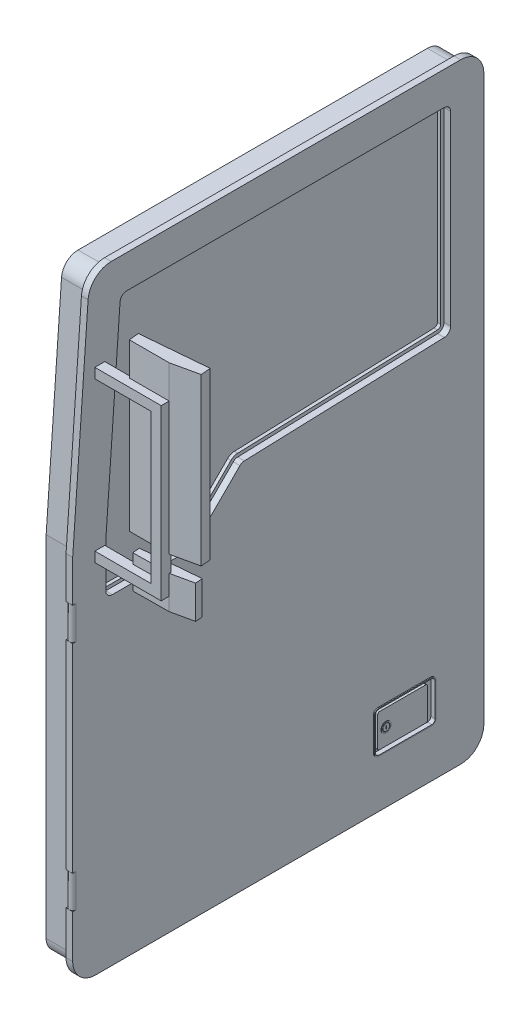
SolidWorks part; units mm, degrees
ref_plane "Front Plane" through (0, 0, 0) normal (0, 0, 1) x (1, 0, 0)
ref_plane "Top Plane" through (0, 0, 0) normal (0, 1, 0) x (1, 0, 0)
ref_plane "Right Plane" through (0, 0, 0) normal (1, 0, 0) x (0, 0, -1)
ref_plane "Plane1" through (950, 0, 0) normal (1, 0, 0) x (0, 0, -1)
sketch "Sketch1" plane through (950, 0, 0) normal (1, 0, 0) x (0, 0, -1)
  line L0 (-750, -200) -> (-750, 1110) construction
  line L1 (-550, 0) -> (550, 0)
  line L2 (-600, 50) -> (-600, 1104.6439)
  line L3 (-503.7259, 1800) -> (550, 1800)
  line L4 (600, 50) -> (600, 1750)
  line L5 (-750, 1110) -> (-699.9479, 1809.9761) construction
  line L6 (-699.9479, 1809.9761) -> (-739.9479, 1809.9761) construction
  line L7 (-739.9479, 1809.9761) -> (-739.9479, 1909.9761) construction
  line L8 (-750, -200) -> (600, -200) construction
  line L9 (600, -200) -> (600, 0) construction
  line L10 (-600, 1104.6439) -> (-553.5985, 1753.5662)
  line L11 (-503.7259, 1820) -> (550, 1820)
  line L12 (620, 50) -> (620, 1750)
  line L13 (-550, -20) -> (550, -20)
  line L14 (-620, 50) -> (-620, 1105.3581)
  line L15 (-620, 1105.3581) -> (-573.5476, 1754.9926)
  arc A0 (-553.5985, 1753.5662) -> (-503.7259, 1800) centre (-503.7259, 1750) cw
  arc A1 (550, 1800) -> (600, 1750) centre (550, 1750) cw
  arc A2 (550, 0) -> (600, 50) centre (550, 50) ccw
  arc A3 (-550, 0) -> (-600, 50) centre (-550, 50) cw
  arc A4 (550, 1820) -> (620, 1750) centre (550, 1750) cw
  arc A5 (550, -20) -> (620, 50) centre (550, 50) ccw
  arc A6 (-550, -20) -> (-620, 50) centre (-550, 50) cw
  arc A7 (-573.5476, 1754.9926) -> (-503.7259, 1820) centre (-503.7259, 1750) cw
  point P16 (600, 1800)
  point P22 (-600, 0)
  dimension "D11" = 50
  dimension "D1" = 1200
  dimension "D2" = 1800
  dimension "D3" = 200
  dimension "D4" = 100
  dimension "D5" = 40
  dimension "D6" = 2110
  dimension "D7" = 150
  dimension "D8" = 1310
  dimension "D9" = 175.91
  dimension "D10" = 150
  dimension "D12" = 20
extrude "Boss-Extrude1" add sketch "Sketch1" against normal blind 20
extrude "Boss-Extrude2" add sketch "Sketch1<2>" against normal blind 100 contours A3 L1 A2 L4 A1 L3 A0 L10 L2 region at (950, 894.6381, -4.6785)
sketch "Sketch1<2>" plane through (950, 0, 0) normal (1, 0, 0) x (0, 0, -1) same geometry as "Sketch1"
sketch "Sketch2" plane through (950, 0, 0) normal (1, 0, 0) x (0, 0, -1)
  line L9 (-520.2547, 1098.2257) -> (-520.2547, 968.2257)
  line L10 (-500.2547, 948.2257) -> (-268.6753, 948.2257)
  line L11 (-254.5499, 954.0669) -> (-115.6202, 1092.6683)
  line L12 (520, 50) -> (520, 1720)
  line L13 (520, 1720) -> (-475.7944, 1720)
  line L14 (-475.7944, 1720) -> (-520.2547, 1098.2257)
  line L15 (520, 1139.3207) -> (520, 1700)
  line L16 (500, 1720) -> (-457.1735, 1720)
  line L17 (-477.1225, 1701.4265) -> (-520.2547, 1098.2257)
  line L18 (-102.1855, 1098.4975) -> (500.6908, 1119.3327)
  line L19 (500, 1710) -> (-457.1735, 1710)
  line L20 (-467.148, 1700.7132) -> (-510.2547, 1097.8687)
  line L21 (-510.2547, 1097.8687) -> (-510.2547, 968.2257)
  line L22 (-500.2547, 958.2257) -> (-268.6753, 958.2257)
  line L23 (-261.6126, 961.1463) -> (-122.6829, 1099.7477)
  line L24 (-102.5309, 1108.4915) -> (500.3454, 1129.3267)
  line L25 (510, 1139.3207) -> (510, 1700)
  arc A6 (520, 1700) -> (500, 1720) centre (500, 1700) ccw
  arc A7 (500.6908, 1119.3327) -> (520, 1139.3207) centre (500, 1139.3207) ccw
  arc A8 (-115.6202, 1092.6683) -> (-102.1855, 1098.4975) centre (-101.4948, 1078.5094) cw
  arc A9 (-268.6753, 948.2257) -> (-254.5499, 954.0669) centre (-268.6753, 968.2257) ccw
  arc A10 (-457.1735, 1720) -> (-477.1225, 1701.4265) centre (-457.1735, 1700) ccw
  arc A11 (-520.2547, 968.2257) -> (-500.2547, 948.2257) centre (-500.2547, 968.2257) ccw
  arc A12 (-457.1735, 1710) -> (-467.148, 1700.7132) centre (-457.1735, 1700) ccw
  arc A13 (-510.2547, 968.2257) -> (-500.2547, 958.2257) centre (-500.2547, 968.2257) ccw
  arc A14 (-268.6753, 958.2257) -> (-261.6126, 961.1463) centre (-268.6753, 968.2257) ccw
  arc A15 (-122.6829, 1099.7477) -> (-102.5309, 1108.4915) centre (-101.4948, 1078.5094) cw
  arc A16 (500.3454, 1129.3267) -> (510, 1139.3207) centre (500, 1139.3207) ccw
  arc A17 (510, 1700) -> (500, 1710) centre (500, 1700) ccw
  point P13 (520, 1120)
  point P16 (-110.0496, 1098.2257)
  point P19 (-260.4048, 948.2257)
  point P25 (-520.2547, 948.2257)
  dimension "D6" = 20
  dimension "D2" = 600
  dimension "D3" = 621.7743
  dimension "D4" = 150
  dimension "D5" = 150
  dimension "D1" = 100
  dimension "D7" = 10
extrude "Cut-Extrude1" cut sketch "Sketch2" against normal blind 20
extrude "Cut-Extrude2" cut sketch "Sketch2<2>" against normal blind 30 contours L25 A17 L19 A12 L20 L21 A13 L22 A14 L23 A15 L24 A16 region at (950, 1382.3885, 18.9303)
sketch "Sketch2<2>" plane through (950, 0, 0) normal (1, 0, 0) x (0, 0, -1) same geometry as "Sketch2"
sketch "Sketch3" plane through (850, 0, 0) normal (-1, 0, 0) x (0, 0, 1)
  line L0 (-520, 1700) -> (-520, 1139.3207)
  line L1 (-500, 1710) -> (457.1735, 1710)
  line L2 (-500.6908, 1119.3327) -> (102.1855, 1098.4975)
  line L3 (115.6202, 1092.6683) -> (254.5499, 954.0669)
  line L4 (268.6753, 948.2257) -> (500.2547, 948.2257)
  line L5 (520.2547, 968.2257) -> (520.2547, 1098.2257)
  line L6 (520.2547, 1098.2257) -> (477.1225, 1701.4265)
  line L7 (-500, 1720) -> (457.1735, 1720)
  line L8 (510.2547, 1097.8687) -> (467.148, 1700.7132)
  line L9 (510.2547, 968.2257) -> (510.2547, 1097.8687)
  line L10 (268.6753, 958.2257) -> (500.2547, 958.2257)
  line L11 (122.6829, 1099.7477) -> (261.6126, 961.1463)
  line L12 (-500.3454, 1129.3267) -> (102.5309, 1108.4915)
  line L13 (-510, 1700) -> (-510, 1139.3207)
  arc A0 (-520, 1139.3207) -> (-500.6908, 1119.3327) centre (-500, 1139.3207) ccw
  arc A1 (102.1855, 1098.4975) -> (115.6202, 1092.6683) centre (101.4948, 1078.5094) cw
  arc A2 (254.5499, 954.0669) -> (268.6753, 948.2257) centre (268.6753, 968.2257) ccw
  arc A5 (254.5499, 954.0669) -> (268.6753, 948.2257) centre (268.6753, 968.2257) ccw construction
  arc A6 (500.2547, 948.2257) -> (520.2547, 968.2257) centre (500.2547, 968.2257) ccw
  arc A7 (457.1735, 1720) -> (477.1225, 1701.4265) centre (457.1735, 1700) cw
  arc A8 (-520, 1700) -> (-500, 1720) centre (-500, 1700) cw
  arc A9 (-510, 1700) -> (-500, 1710) centre (-500, 1700) cw
  arc A10 (457.1735, 1710) -> (467.148, 1700.7132) centre (457.1735, 1700) cw
  arc A11 (500.2547, 958.2257) -> (510.2547, 968.2257) centre (500.2547, 968.2257) ccw
  arc A12 (261.6126, 961.1463) -> (268.6753, 958.2257) centre (268.6753, 968.2257) ccw
  arc A13 (102.5309, 1108.4915) -> (122.6829, 1099.7477) centre (101.4948, 1078.5094) cw
  arc A14 (-510, 1139.3207) -> (-500.3454, 1129.3267) centre (-500, 1139.3207) ccw
  dimension "D1" = 10
extrude "Cut-Extrude3" cut sketch "Sketch3" against normal blind 20
extrude "Cut-Extrude4" cut sketch "Sketch3<2>" against normal blind 60 contours L13 A14 L12 A13 L11 A12 L10 A11 L9 L8 A10 L1 A9 region at (850, 1382.3885, 18.9303)
sketch "Sketch3<2>" plane through (850, 0, 0) normal (-1, 0, 0) x (0, 0, 1) same geometry as "Sketch3"
ref_plane "Plane2" through (0, 180, 0) normal (0, -1, 0) x (1, 0, 0)
sketch "Sketch4" plane through (0, 180, 0) normal (0, -1, 0) x (1, 0, 0)
  line L0 (930, 573.5476) -> (930, 620) construction
  line L2 (930, 620) -> (950, 620) construction
  line L3 (930, 610) -> (930, 624.5561)
  line L4 (930, 624.5561) -> (950, 624.5561)
  line L5 (950, 624.5561) -> (950, 610)
  circle A0 centre (940, 610) radius 10
  dimension "D1" = 20
extrude "Cut-Extrude5" cut sketch "Sketch4" against normal blind 100 contours A0 L5 L4 L3 region at (940, 180, 620.8334)
pattern_linear "LPattern1" count 2 spacing 700 along (0, 1, 0) of "Cut-Extrude5"
sketch "Sketch5" plane through (950, 0, 0) normal (1, 0, 0) x (0, 0, -1)
  line L0 (620, 50) -> (620, 1750) construction
  line L1 (460, 130) -> (300, 130)
  line L2 (470, 140) -> (470, 240)
  line L3 (460, 250) -> (300, 250)
  line L4 (290, 140) -> (290, 240)
  line L5 (-550, -20) -> (550, -20) construction
  line L6 (460, 253) -> (300, 253)
  line L7 (287, 140) -> (287, 240)
  line L8 (460, 127) -> (300, 127)
  line L9 (473, 140) -> (473, 240)
  arc A0 (470, 240) -> (460, 250) centre (460, 240) ccw
  arc A1 (460, 130) -> (470, 140) centre (460, 140) ccw
  arc A2 (300, 130) -> (290, 140) centre (300, 140) cw
  arc A3 (300, 250) -> (290, 240) centre (300, 240) ccw
  arc A4 (300, 253) -> (287, 240) centre (300, 240) ccw
  arc A5 (300, 127) -> (287, 140) centre (300, 140) cw
  arc A6 (460, 127) -> (473, 140) centre (460, 140) ccw
  arc A7 (473, 240) -> (460, 253) centre (460, 240) ccw
  point P10 (470, 250)
  point P13 (470, 130)
  point P16 (290, 130)
  dimension "D5" = 10
  dimension "D1" = 120
  dimension "D2" = 150
  dimension "D3" = 150
  dimension "D4" = 180
  dimension "D6" = 3
extrude "Cut-Extrude6" cut sketch "Sketch5" against normal blind 10 contours L3 A3 L4 A2 L1 A1 L2 A0 region at (950, 190, -380)
extrude "Boss-Extrude3" add sketch "Sketch5<3>" along normal blind 3
sketch "Sketch5<3>" plane through (950, 0, 0) normal (1, 0, 0) x (0, 0, -1) same geometry as "Sketch5"
sketch "Sketch6" plane through (940, 0, 0) normal (1, 0, 0) x (0, 0, -1)
  line L0 (300, 130) -> (460, 130) construction
  line L1 (305, 240) -> (445, 240)
  line L2 (300, 235) -> (300, 145)
  line L3 (305, 140) -> (445, 140)
  line L4 (450, 235) -> (450, 145)
  line L5 (290, 240) -> (290, 140) construction
  arc A0 (300, 145) -> (305, 140) centre (305, 145) ccw
  arc A1 (445, 140) -> (450, 145) centre (445, 145) ccw
  arc A2 (445, 240) -> (450, 235) centre (445, 235) cw
  arc A3 (305, 240) -> (300, 235) centre (305, 235) ccw
  point P10 (300, 140)
  point P15 (450, 240)
  point P18 (300, 240)
  dimension "D5" = 5
  dimension "D1" = 150
  dimension "D2" = 100
  dimension "D3" = 10
  dimension "D4" = 10
extrude "Boss-Extrude4" add sketch "Sketch6" along normal blind 10
sketch "Sketch10" plane through (950, 0, 0) normal (1, 0, 0) x (0, 0, -1)
  line L0 (324.7973, 190) -> (300, 190) construction
  line L1 (325.7973, 195) -> (323.7973, 195)
  line L2 (325.7973, 195) -> (325.7973, 185)
  line L3 (325.7973, 185) -> (323.7973, 185)
  line L4 (323.7973, 195) -> (323.7973, 185)
  line L5 (325.7973, 195) -> (323.7973, 185) construction
  line L6 (325.7973, 185) -> (323.7973, 195) construction
  line L7 (300, 235) -> (300, 145) construction
  circle A0 centre (324.7973, 190) radius 15
  dimension "D1" = 30
  dimension "D2" = 2
  dimension "D3" = 10
extrude "Boss-Extrude5" add sketch "Sketch10" along normal blind 1
extrude "Cut-Extrude8" cut sketch "Sketch10<2>" against normal blind 20 contours L1 L4 L3 L2 region at (950, 190, -324.7973)
sketch "Sketch10<2>" plane through (950, 0, 0) normal (1, 0, 0) x (0, 0, -1) same geometry as "Sketch10"
sketch "Sketch11" plane through (951, 0, 0) normal (1, 0, 0) x (0, 0, -1)
  circle A0 centre (324.7973, 190) radius 10.3287
extrude "Cut-Extrude-Thin1" cut sketch "Sketch11" against normal blind 5 thin thin type one direction wall 1
sketch "Sketch12" plane through (950, 0, 0) normal (1, 0, 0) x (0, 0, -1)
  line L0 (-477.1225, 1701.4265) -> (-520.2547, 1098.2257) construction
  line L1 (-523.1149, 1058.2257) -> (-553.1149, 1058.2257)
  line L2 (-523.1149, 1058.2257) -> (-523.1149, 1088.2257)
  line L3 (-523.1149, 1088.2257) -> (-553.1149, 1088.2257)
  line L4 (-553.1149, 1058.2257) -> (-553.1149, 1088.2257)
  line L5 (-500.2547, 958.2257) -> (-268.6753, 958.2257) construction
  line L6 (-523.1149, 1568.2257) -> (-553.1149, 1568.2257)
  line L7 (-523.1149, 1568.2257) -> (-523.1149, 1538.2257)
  line L8 (-523.1149, 1538.2257) -> (-553.1149, 1538.2257)
  line L9 (-553.1149, 1568.2257) -> (-553.1149, 1538.2257)
  dimension "D1" = 30
  dimension "D2" = 30
  dimension "D3" = 30
  dimension "D4" = 30
  dimension "D5" = 450
  dimension "D6" = 100
extrude "Boss-Extrude6" add sketch "Sketch12" along normal blind 200
sketch "Sketch13" plane through (1150, 0, 0) normal (1, 0, 0) x (0, 0, -1)
  line L0 (-553.1149, 1058.2257) -> (-523.1149, 1058.2257) construction
  line L1 (-553.1149, 1568.2257) -> (-523.1149, 1568.2257)
  line L2 (-553.1149, 1568.2257) -> (-553.1149, 1058.2257)
  line L3 (-553.1149, 1058.2257) -> (-523.1149, 1058.2257)
  line L4 (-523.1149, 1568.2257) -> (-523.1149, 1058.2257)
  line L5 (-523.1149, 1058.2257) -> (-523.1149, 1088.2257) construction
extrude "Boss-Extrude7" add sketch "Sketch13" against normal blind 30
ref_plane "Plane3" through (0, 1668.2257, 0) normal (0, 1, 0) x (-1, 0, 0)
sketch "Sketch14" plane through (0, 1668.2257, 0) normal (0, 1, 0) x (-1, 0, 0)
  line L0 (-1030, 529.1365) -> (-1229.2389, 511.7053) construction
  line L1 (-1030, 529.1365) -> (-1027.3853, 499.2506)
  line L2 (-1229.2389, 511.7053) -> (-1226.6243, 481.8195)
  line L3 (-1027.3853, 499.2506) -> (-1226.6243, 481.8195)
  line L4 (-1030, 529.1365) -> (-1150, 529.1365)
  line L5 (-1150, 523.1149) -> (-1150, 553.1149) construction
  line L6 (-950, 573.5476) -> (-950, 503.7259) construction
  line L7 (-1150, 529.1365) -> (-1229.2389, 511.7053)
  dimension "D1" = 5
  dimension "D2" = 200
  dimension "D3" = 80
  dimension "D4" = 30
extrude "Boss-Extrude8" add sketch "Sketch14" against normal blind 500
sketch "Sketch15" plane through (51.1511, 0, 584.66) normal (-0.0872, 0, -0.9962) x (-0.9962, 0, 0.0872)
  line L12 (-983.9633, 1664.2257) -> (-1175.9633, 1664.2257)
  line L13 (-1175.9633, 1664.2257) -> (-1175.9633, 1172.2257)
  line L14 (-1175.9633, 1172.2257) -> (-983.9633, 1172.2257)
  line L15 (-983.9633, 1172.2257) -> (-983.9633, 1664.2257)
  line L16 (-983.9633, 1664.2257) -> (-1175.9633, 1664.2257)
  line L17 (-1175.9633, 1664.2257) -> (-1175.9633, 1172.2257)
  line L18 (-1175.9633, 1172.2257) -> (-983.9633, 1172.2257)
  line L19 (-983.9633, 1172.2257) -> (-983.9633, 1664.2257)
  dimension "D1" = 4
extrude "Cut-Extrude9" cut sketch "Sketch15" against normal blind 10
sketch "Sketch16" plane through (52.0227, 0, 594.622) normal (-0.0872, 0, -0.9962) x (-0.9962, 0, 0.0872)
  line L0 (-1175.9633, 1172.2257) -> (-983.9633, 1172.2257) construction
  line L1 (-983.9633, 1172.2257) -> (-983.9633, 1664.2257) construction
  circle A0 centre (-1053.9633, 1242.2257) radius 50
  dimension "D3" = 100
  dimension "D1" = 70
  dimension "D2" = 70
extrude "Boss-Extrude9" add sketch "Sketch16" along normal blind 0.5
dome "Dome1" faces to dome 1 distance 5 reverse direction no elliptical dome no face at (1052.122, 1242.2257, 506.6227) parameters "D1"=5
ref_plane "Plane4" through (0, 1118.2257, 0) normal (0, -1, 0) x (1, 0, 0)
sketch "Sketch18" plane through (0, 1118.2257, 0) normal (0, -1, 0) x (1, 0, 0)
  line L0 (1039.3644, 508.2408) -> (1213.6985, 492.9885)
  line L1 (1039.3644, 508.2408) -> (1041.2644, 529.9582)
  line L2 (1213.6985, 492.9885) -> (1215.5985, 514.706)
  line L3 (1041.2644, 529.9582) -> (1215.5985, 514.706) construction
  line L5 (1226.6243, 481.8195) -> (1027.3853, 499.2506) construction
  line L6 (1215.5985, 514.706) -> (1150, 529.1365)
  line L7 (1150, 553.1149) -> (1150, 523.1149) construction
  line L8 (1150, 529.1365) -> (1229.2389, 511.7053) construction
  line L9 (1150, 529.1365) -> (1041.2644, 529.9582)
  dimension "D1" = 10
  dimension "D2" = 175
extrude "Boss-Extrude10" add sketch "Sketch18" along normal blind 100
sketch "Sketch19" plane through (850, 0, 0) normal (-1, 0, 0) x (0, 0, 1)
  line L0 (-517.1737, 1027.2796) -> (80.5914, 1001.2898)
  line L1 (80.5914, 1001.2898) -> (267.2454, 864.2527)
  line L2 (267.2454, 864.2527) -> (267.2454, 748.48)
  line L3 (267.2454, 748.48) -> (-517.1737, 748.48)
  line L4 (-517.1737, 748.48) -> (-517.1737, 1027.2796)
  line L5 (267.2454, 581.3838) -> (267.2454, 406.5274)
  line L6 (267.2454, 406.5274) -> (173.9184, 325.1988)
  line L7 (173.9184, 325.1988) -> (-517.1737, 325.1988)
  line L8 (-517.1737, 325.1988) -> (-517.1737, 581.3838)
  line L9 (263.2454, 581.3838) -> (263.2454, 408.3473)
  line L10 (263.2454, 408.3473) -> (172.4201, 329.1988)
  line L11 (172.4201, 329.1988) -> (-513.1737, 329.1988)
  line L12 (-513.1737, 329.1988) -> (-513.1737, 581.3838)
  line L13 (-517.1737, 581.3838) -> (-513.1737, 581.3838)
  line L14 (267.2454, 581.3838) -> (263.2454, 581.3838)
  dimension "D1" = 4
extrude "Boss-Extrude11" add sketch "Sketch19" along normal blind 50
sketch "Sketch20" plane through (800, 0, 0) normal (-1, 0, 0) x (0, 0, 1)
  line L0 (-517.1737, 581.3838) -> (267.2454, 581.3838)
  line L1 (267.2454, 581.3838) -> (267.2454, 406.5274)
  line L2 (267.2454, 406.5274) -> (173.9184, 325.1988)
  line L3 (173.9184, 325.1988) -> (-517.1737, 325.1988)
  line L4 (-517.1737, 325.1988) -> (-517.1737, 581.3838)
  line L5 (-517.1737, 900) -> (-517.1737, 748.48)
  line L6 (-517.1737, 748.48) -> (267.2454, 748.48)
  line L7 (267.2454, 748.48) -> (267.2454, 864.2527)
  line L8 (267.2454, 864.2527) -> (-171.6276, 900)
  line L9 (-171.6276, 900) -> (-517.1737, 900)
extrude "Boss-Extrude12" add sketch "Sketch20" along normal blind 5
sketch "Sketch21" plane through (800, 0, 0) normal (-1, 0, 0) x (0, 0, 1)
  line L1 (74.7593, 974.3228) -> (-40.7347, 974.3228)
  line L2 (74.7593, 974.3228) -> (74.7593, 909.2873)
  line L3 (74.7593, 909.2873) -> (-40.7347, 909.2873)
  line L4 (-40.7347, 974.3228) -> (-40.7347, 909.2873)
extrude "Cut-Extrude10" cut sketch "Sketch21" against normal blind 15
sketch "Sketch22" plane through (815, 0, 0) normal (-1, 0, 0) x (0, 0, 1)
  line L0 (-40.7347, 974.3228) -> (-40.7347, 909.2873) construction
  line L1 (-40.7347, 971.0503) -> (-10.489, 971.0503)
  line L2 (-40.7347, 971.0503) -> (-40.7347, 913.1895)
  line L3 (-40.7347, 913.1895) -> (-4.3054, 913.1895)
  line L4 (-4.3054, 934.3904) -> (-4.3054, 913.1895)
  line L5 (-10.489, 971.0503) -> (-4.3054, 934.3904)
extrude "Boss-Extrude13" add sketch "Sketch22" along normal blind 5
sketch "Sketch23" plane through (810, 0, 0) normal (-1, 0, 0) x (0, 0, 1)
  line L0 (-40.7347, 971.0503) -> (-10.489, 971.0503)
  line L1 (-10.489, 971.0503) -> (-4.3054, 934.3904)
  line L2 (-4.3054, 934.3904) -> (68.5727, 934.3904)
  line L3 (68.5727, 934.3904) -> (68.5727, 913.1895)
  line L4 (68.5727, 913.1895) -> (-40.7347, 913.1895)
  line L5 (-40.7347, 913.1895) -> (-40.7347, 971.0503)
extrude "Boss-Extrude14" add sketch "Sketch23" along normal blind 8
sketch "Sketch24" plane through (800, 0, 0) normal (-1, 0, 0) x (0, 0, 1)
  line L0 (-44.7347, 976.3228) -> (-44.7347, 907.2873)
  line L1 (-40.7347, 974.3228) -> (74.7593, 974.3228)
  line L2 (-40.7347, 974.3228) -> (-40.7347, 909.2873)
  line L3 (-40.7347, 909.2873) -> (74.7593, 909.2873)
  line L4 (74.7593, 974.3228) -> (74.7593, 909.2873)
  line L5 (-42.7347, 905.2873) -> (76.7593, 905.2873)
  line L6 (78.7593, 976.3228) -> (78.7593, 907.2873)
  line L7 (-42.7347, 978.3228) -> (76.7593, 978.3228)
  line L8 (-44.7347, 978.3228) -> (-44.7347, 905.2873) construction
  line L9 (-44.7347, 905.2873) -> (78.7593, 905.2873) construction
  line L10 (78.7593, 978.3228) -> (78.7593, 905.2873) construction
  line L11 (-44.7347, 978.3228) -> (78.7593, 978.3228) construction
  arc A0 (-44.7347, 907.2873) -> (-42.7347, 905.2873) centre (-42.7347, 907.2873) ccw
  arc A1 (76.7593, 905.2873) -> (78.7593, 907.2873) centre (76.7593, 907.2873) ccw
  arc A2 (78.7593, 976.3228) -> (76.7593, 978.3228) centre (76.7593, 976.3228) ccw
  arc A3 (-44.7347, 976.3228) -> (-42.7347, 978.3228) centre (-42.7347, 976.3228) cw
  dimension "D2" = 2
  dimension "D1" = 4
extrude "Boss-Extrude15" add sketch "Sketch24" along normal blind 2
sketch "Sketch25" plane through (815, 0, 0) normal (-1, 0, 0) x (0, 0, 1)
  line L0 (-9.0127, 974.3228) -> (1.9571, 909.2873)
  line L1 (74.7593, 974.3228) -> (-40.7347, 974.3228) construction
  line L2 (-40.7347, 909.2873) -> (74.7593, 909.2873) construction
  line L3 (1.9571, 909.2873) -> (74.7593, 909.2873)
  line L4 (74.7593, 909.2873) -> (74.7593, 974.3228)
  line L5 (74.7593, 909.2873) -> (74.7593, 974.3228) construction
  line L6 (74.7593, 909.2873) -> (74.7593, 974.3228) construction
  line L7 (74.7593, 974.3228) -> (-9.0127, 974.3228)
  line L8 (-4.3054, 934.3904) -> (-10.489, 971.0503) construction
  line L9 (-4.3054, 934.3904) -> (-10.489, 971.0503) construction
  dimension "D1" = 2
extrude "Cut-Extrude11" cut sketch "Sketch25" against normal blind 20
